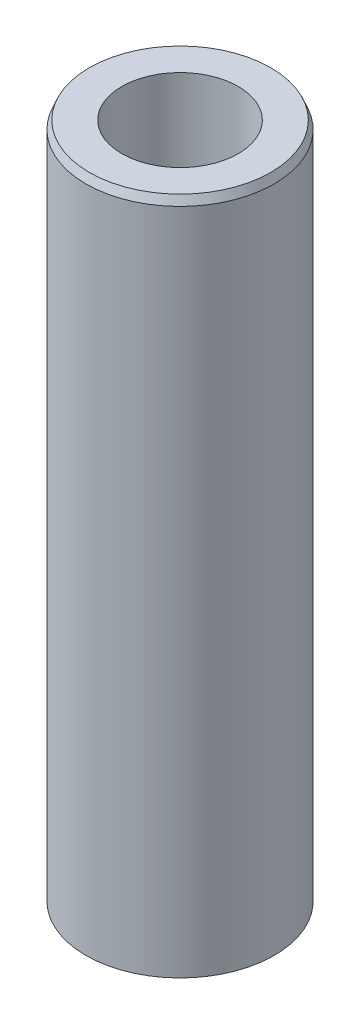
SolidWorks part; units mm, degrees
ref_plane "Front Plane" through (0, 0, 0) normal (0, 0, 1) x (1, 0, 0)
ref_plane "Top Plane" through (0, 0, 0) normal (0, 1, 0) x (1, 0, 0)
ref_plane "Right Plane" through (0, 0, 0) normal (1, 0, 0) x (0, 0, -1)
sketch "Sketch1" plane through (0, 0, 0) normal (0, 1, 0) x (1, 0, 0)
  circle A0 centre (0, 0) radius 40
  dimension "SHAFT_OD" = 80
extrude "Boss-Extrude1" add sketch "Sketch1" along normal blind 288.8566
sketch "Sketch2" plane through (0, 0, 0) normal (0, 1, 0) x (1, 0, 0)
  circle A0 centre (0, 0) radius 24.7432
  dimension "BORE_D" = 49.4863
extrude "Cut-Extrude1" cut sketch "Sketch2" along normal through all
chamfer "Chamfer1" distance 3.5027 angle 22.546 2 edges at (0, 288.8566, 40) (0, 0, 40) first distance on face at (0, 288.8566, 40) first distance on face at (0, 0, 24.7432)
